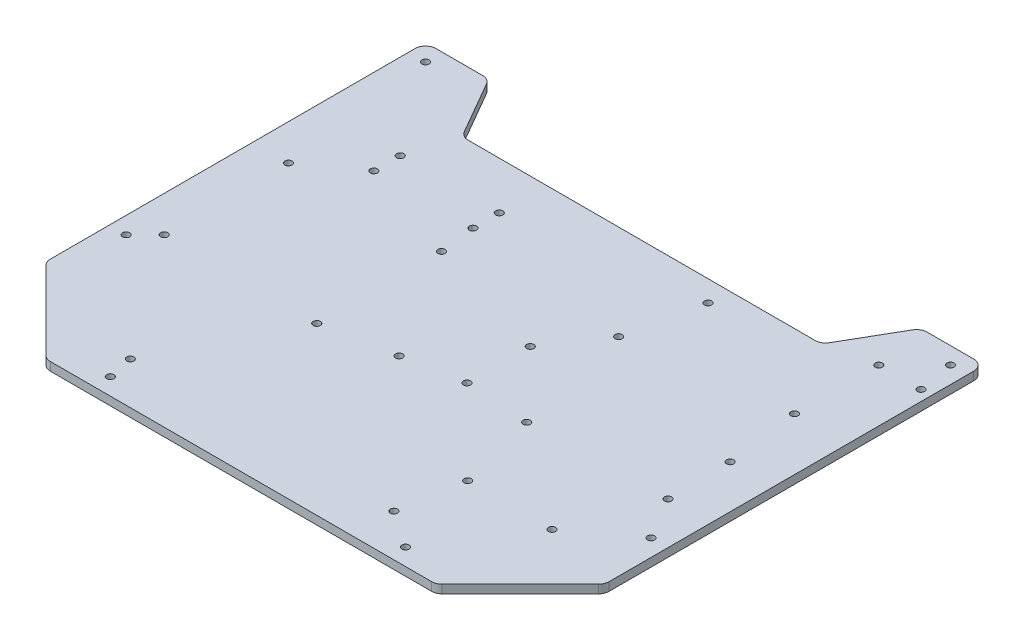
SolidWorks part; units mm, degrees
material "Acier non allié"
ref_plane "Front" through (0, 0, 0) normal (0, 0, 1) x (1, 0, 0)
ref_plane "Top" through (0, 0, 0) normal (0, 1, 0) x (1, 0, 0)
ref_plane "Right" through (0, 0, 0) normal (1, 0, 0) x (0, 0, -1)
sketch "Main scetch" plane through (0, 0, 0) normal (0, 1, 0) x (1, 0, 0)
  line L1 (0, 0) -> (132.5, 0) construction
  line L2 (0, 0) -> (0, 220) construction
  line L3 (0, 220) -> (132.5, 220) construction
  line L4 (132.5, 0) -> (132.5, 220) construction
  line L13 (-92.5, 0) -> (92.5, 0)
  line L14 (92.5, 0) -> (132.5, 40)
  line L15 (132.5, 40) -> (132.5, 220)
  line L16 (132.5, 220) -> (102.5, 220)
  line L17 (102.5, 220) -> (85.1795, 190)
  line L18 (85.1795, 190) -> (-85.1795, 190)
  line L19 (-102.5, 220) -> (-85.1795, 190)
  line L20 (-132.5, 220) -> (-102.5, 220)
  line L21 (-132.5, 40) -> (-132.5, 220)
  line L22 (-92.5, 0) -> (-132.5, 40)
  point P11 (0, 190)
  dimension "132.5" = 132.5
  dimension "D2" = 220
  dimension "D1" = 40
  dimension "D3" = 40
  dimension "D4" = 30
  dimension "D5" = 60
  dimension "D6" = 30
extrude "Main extrusion" add sketch "Main scetch" along normal blind 4
fillet "Congé1" radius 5 10 edges at (-132.5, 2, -40) (-92.5, 2, 0) (92.5, 2, 0) (132.5, 2, -40) (132.5, 2, -220) (102.5, 2, -220) (85.1795, 2, -190) (-85.1795, 2, -190) (-102.5, 2, -220) (-132.5, 2, -220)
sketch "Esquisse1" plane through (0, 4, 0) normal (0, 1, 0) x (1, 0, 0)
  line L0 (0, 0) -> (0, 218.5516) construction
  line L1 (132.5, 42.0711) -> (132.5, 215) construction
  line L2 (127.5, 220) -> (105.3868, 220) construction
  line L3 (-90.4289, 0) -> (90.4289, 0) construction
  circle A0 centre (70, 8) radius 1
  circle A1 centre (124.5, 70) radius 1
  circle A2 centre (124.5, 212) radius 1
  circle A3 centre (-124.5, 212) radius 1
  circle A4 centre (-124.5, 70) radius 1
  circle A5 centre (-70, 8) radius 1
  dimension "D1" = 2
  dimension "D2" = 2
  dimension "D3" = 2
  dimension "D4" = 8
  dimension "D5" = 8
  dimension "D6" = 8
  dimension "D7" = 8
  dimension "D8" = 70
  dimension "D9" = 70
extrude "Enlèv. mat.-Extru.1" cut sketch "Esquisse1" against normal through all
hole_wizard "Dégagement M31" positions "Esquisse2" profile "Esquisse3" hole size "M3" standard "ISO" end condition through all
sketch "Esquisse2" plane through (0, 4, 0) normal (0, 1, 0) x (1, 0, 0)
  point P0 (-124.5, 212)
  point P3 (-124.5, 70)
  point P6 (-70, 8)
  point P9 (70, 8)
  point P12 (124.5, 70)
  point P15 (124.5, 212)
sketch "Esquisse3" plane through (-124.5, 4, -212) normal (1, 0, 0) x (0, 0, 1)
  line L0 (0, 0) -> (0, 4)
  line L1 (0, 4) -> (1.7, 4)
  line L2 (1.7, 4) -> (1.7, 0)
  line L5 (1.7, 0) -> (0, 0)
  line L11 (0, -6.35) -> (0, 107.95) construction
  dimension "Diamètre du perçage jusqu'au prochain" = 3.4
  dimension "Profondeur du perçage jusqu'au prochain" = 4
sketch "Esquisse4" plane through (0, 4, 0) normal (0, 1, 0) x (1, 0, 0)
  line L0 (-132.5, 215) -> (-132.5, 42.0711) construction
  line L2 (82.2927, 190) -> (-82.2927, 190) construction
  line L3 (132.5, 42.0711) -> (132.5, 215) construction
  line L4 (-90.4289, 0) -> (90.4289, 0) construction
  line L5 (127.5, 220) -> (105.3868, 220) construction
  circle A1 centre (-68.5, 185) radius 1 construction
  circle A5 centre (41.5, 180) radius 1
  circle A6 centre (34.12, 145) radius 1
  circle A7 centre (107.5, 155) radius 1
  circle A8 centre (127.5, 195) radius 1
  circle A9 centre (112, 120) radius 1
  circle A10 centre (112.5, 90) radius 1
  circle A11 centre (17.2, 120) radius 1
  circle A12 centre (17.2, 90) radius 1
  circle A13 centre (47.5, 88) radius 1
  circle A14 centre (57.5, 50) radius 1
  circle A15 centre (97.5, 50) radius 1
  circle A16 centre (52.5, 20) radius 1
  circle A17 centre (-10, 85) radius 1
  circle A18 centre (-72.5, 20) radius 1
  circle A19 centre (107.5, 195) radius 1
  circle A23 centre (-115.5, 138) radius 1
  circle A24 centre (-42.86, 138) radius 1
  circle A25 centre (-115.5, 79.07) radius 1
  circle A26 centre (-42.8904, 78.82) radius 1
  circle A27 centre (-92, 167.5) radius 1
  circle A28 centre (-45, 167.5) radius 1
  circle A29 centre (-92, 155) radius 1
  circle A30 centre (-45, 155) radius 1
  dimension "D4" = 2
  dimension "D13" = 2
  dimension "D16" = 2
  dimension "D19" = 2
  dimension "D24" = 2
  dimension "D25" = 2
  dimension "D28" = 2
  dimension "D30" = 2
  dimension "D32" = 2
  dimension "D36" = 2
  dimension "D37" = 2
  dimension "D40" = 2
  dimension "D48" = 2
  dimension "D49" = 2
  dimension "D50" = 2
  dimension "D52" = 2
  dimension "D11" = 2
  dimension "D12" = 2
  dimension "D65" = 2
  dimension "D66" = 2
  dimension "D58" = 2
  dimension "D61" = 2
  dimension "D70" = 2
  dimension "D71" = 2
  dimension "D14" = 174
  dimension "D15" = 10
  dimension "D17" = 166.62
  dimension "D18" = 45
  dimension "D20" = 25
  dimension "D21" = 65
  dimension "D22" = 5
  dimension "D23" = 25
  dimension "D26" = 20.5
  dimension "D27" = 100
  dimension "D29" = 30
  dimension "D31" = 115.3
  dimension "D33" = 115.3
  dimension "D34" = 132
  dimension "D35" = 85
  dimension "D38" = 50
  dimension "D39" = 75
  dimension "D41" = 35
  dimension "D42" = 80
  dimension "D43" = 20
  dimension "D44" = 20
  dimension "D45" = 205
  dimension "D46" = 85
  dimension "D47" = 142.5
  dimension "D51" = 25
  dimension "D53" = 25
  dimension "D54" = 5
  dimension "D55" = 64
  dimension "D7" = 59.18
  dimension "D8" = 72.64
  dimension "D9" = 58.93
  dimension "D10" = 72.61
  dimension "D67" = 17
  dimension "D68" = 138
  dimension "D56" = 23.5
  dimension "D57" = 23.5
  dimension "D59" = 17.5
  dimension "D60" = 17.5
  dimension "D62" = 12.5
  dimension "D63" = 12.5
  dimension "D64" = 23.5
  dimension "D69" = 23.5
extrude "Enlèv. mat.-Extru.2" cut sketch "Esquisse4" against normal through all
hole_wizard "Dégagement M32" positions "Esquisse5" profile "Esquisse6" hole size "M3" standard "ISO" end condition through all
sketch "Esquisse5" plane through (0, 4, 0) normal (0, 1, 0) x (1, 0, 0)
  point P9 (17.2, 120)
  point P18 (34.12, 145)
  point P21 (41.5, 180)
  point P24 (107.5, 155)
  point P27 (127.5, 195)
  point P30 (112, 120)
  point P33 (112.5, 90)
  point P36 (47.5, 88)
  point P39 (17.2, 90)
  point P42 (57.5, 50)
  point P45 (97.5, 50)
  point P48 (-10, 85)
  point P51 (-72.5, 20)
  point P54 (52.5, 20)
  point P57 (107.5, 195)
  point P86 (-115.5, 138)
  point P89 (-42.86, 138)
  point P92 (-115.5, 79.07)
  point P95 (-42.8904, 78.82)
  point P102 (-92, 167.5)
  point P105 (-92, 155)
  point P108 (-45, 155)
  point P111 (-45, 167.5)
sketch "Esquisse6" plane through (17.2, 4, -120) normal (1, 0, 0) x (0, 0, 1)
  line L0 (0, 0) -> (0, 4)
  line L1 (0, 4) -> (1.7, 4)
  line L2 (1.7, 4) -> (1.7, 0)
  line L5 (1.7, 0) -> (0, 0)
  line L11 (0, -6.35) -> (0, 107.95) construction
  dimension "Diamètre du perçage jusqu'au prochain" = 3.4
  dimension "Profondeur du perçage jusqu'au prochain" = 4
equation "\"WIDTH\"= 300mm'Total width of the robot"
equation "\"LENGTH\"= 220mm'Total length of the robot"
equation "\"D2@Main scetch\" = \"LENGTH\""
equation "\"CUT_DEPTH\"= 45mm'Depth of the cut on the edges of the plate"
equation "\"Plate_th\"= 3mm'Thickness of the plate"
equation "\"D1\"= \"Plate_th\""
equation "\"D47@Esquisse4\"=(80+205)/2"
